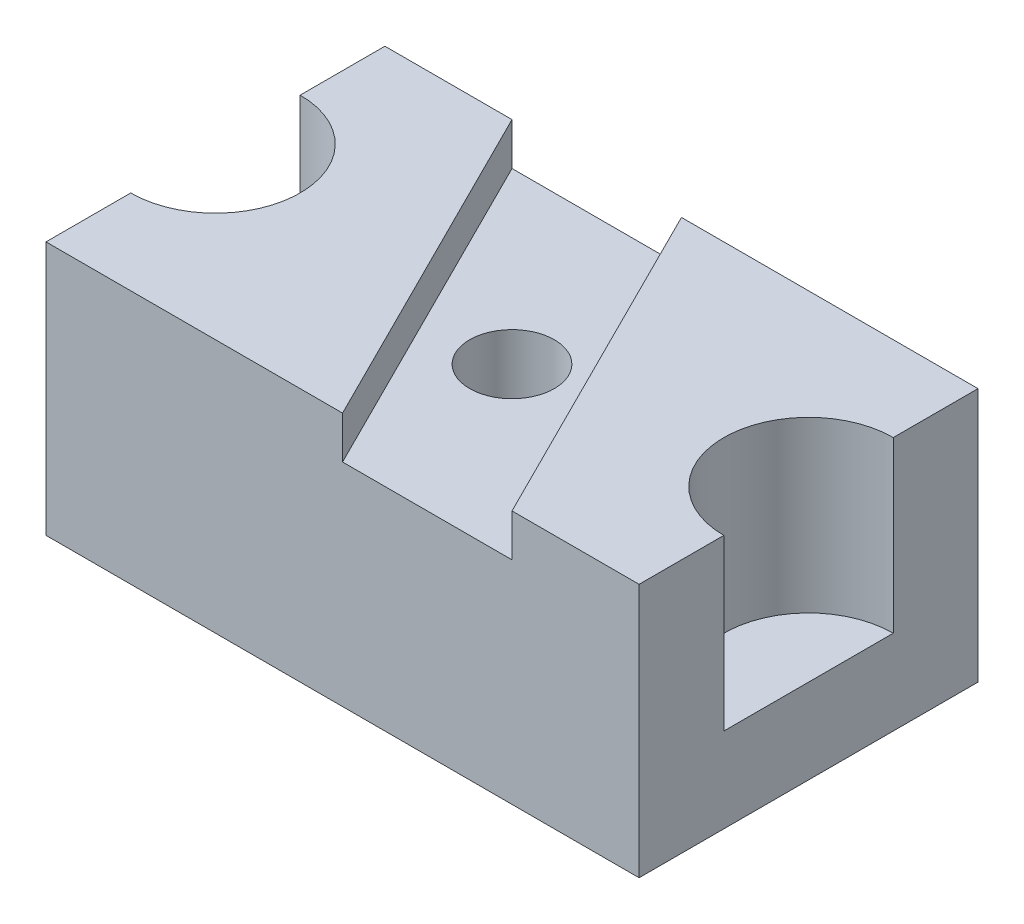
SolidWorks part; units mm, degrees
ref_plane "Front Plane" through (0, 0, 0) normal (0, 0, 1) x (1, 0, 0)
ref_plane "Top Plane" through (0, 0, 0) normal (0, 1, 0) x (1, 0, 0)
ref_plane "Right Plane" through (0, 0, 0) normal (1, 0, 0) x (0, 0, -1)
sketch "Sketch1" plane through (0, 0, 0) normal (0, 1, 0) x (1, 0, 0)
  line L0 (0, -2) -> (-2, 2)
  line L1 (-3.5, -2) -> (3.5, -2)
  line L2 (-3.5, -2) -> (-3.5, 2)
  line L3 (-3.5, 2) -> (3.5, 2)
  line L4 (3.5, -2) -> (3.5, 2)
  line L5 (-3.5, -2) -> (3.5, 2) construction
  line L6 (-3.5, 2) -> (3.5, -2) construction
  line L7 (0, 2) -> (2, -2)
  circle A0 centre (0, 0) radius 0.5
  circle A1 centre (-3.5, 0) radius 1
  circle A2 centre (3.5, 0) radius 1
  point P0 (0, 0)
  dimension "D3" = 1
  dimension "D5" = 2
  dimension "D6" = 2
  dimension "D1" = 4
  dimension "D2" = 7
  dimension "D4" = 2
extrude "Boss-Extrude1" add sketch "Sketch1" along normal blind 1 contours L4 A2 | L2 A1 region at (-3.0756, 0, 0) region at (3.0756, 0, 0)
extrude "Boss-Extrude2" add sketch "Sketch1<3>" along normal blind 3 contours A1 L2 L1 L0 L3 | A2 L4 L3 L7 L1 region at (-2.0171, 0, 0.3164) region at (2.0171, 0, -0.3164)
sketch "Sketch1<3>" plane through (0, 0, 0) normal (0, 1, 0) x (1, 0, 0) same geometry as "Sketch1"
extrude "Boss-Extrude3" add sketch "Sketch1<4>" along normal blind 2.5 contours L7 L3 L0 L1 A0 region at (-0.9494, 0, -0.0253)
sketch "Sketch1<4>" plane through (0, 0, 0) normal (0, 1, 0) x (1, 0, 0) same geometry as "Sketch1"
